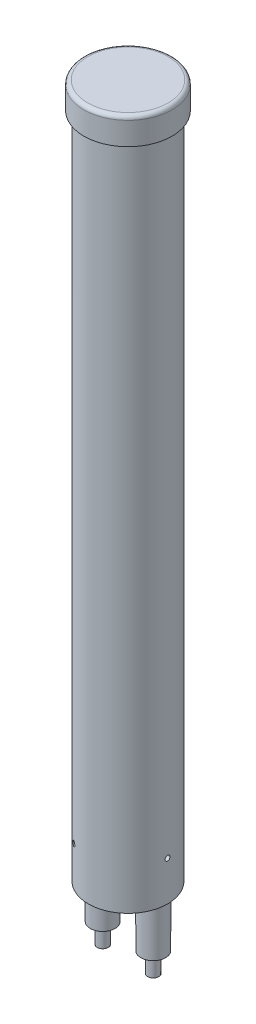
SolidWorks part; units mm, degrees
material "ABS"
ref_plane "Płaszczyzna przednia" through (0, 0, 0) normal (0, 0, 1) x (1, 0, 0)
ref_plane "Płaszczyzna górna" through (0, 0, 0) normal (0, 1, 0) x (1, 0, 0)
ref_plane "Płaszczyzna prawa" through (0, 0, 0) normal (1, 0, 0) x (0, 0, -1)
sketch "Sketch1" plane through (0, 0, 0) normal (0, 1, 0) x (1, 0, 0)
  circle A0 centre (0, 0) radius 20
  dimension "D1" = 40
extrude "Boss-Extrude1" add sketch "Sketch1" along normal blind 345
sketch "Sketch2" plane through (0, 345, 0) normal (0, 1, 0) x (1, 0, 0)
  circle A0 centre (0, 0) radius 22.25
  dimension "D1" = 44.5
extrude "Boss-Extrude2" add sketch "Sketch2" along normal blind 5 and the other way blind 8.5
fillet "Fillet1" radius 2 1 edges at (0, 350, 22.25)
ref_plane "Plane1" through (20, 0, 0) normal (1, 0, 0) x (0, 0, -1)
sketch "Sketch3" plane through (20, 0, 0) normal (1, 0, 0) x (0, 0, -1)
  line L0 (0, 0) -> (0, 20) construction
  circle A0 centre (0, 20) radius 1.25
  dimension "D2" = 2.5
  dimension "D1" = 20
extrude "Cut-Extrude1" cut sketch "Sketch3" against normal blind 5
pattern_circular "CirPattern1" count 3 every 120 about axis through (0, 345, 0) along (0, -1, 0) of "Cut-Extrude1"
sketch "Sketch4" plane through (0, 0, 0) normal (0, -1, 0) x (1, 0, 0)
  line L0 (12.75, 0) -> (0, 0) construction
  line L1 (0, 0) -> (-12.75, 0) construction
  circle A0 centre (-12.75, 0) radius 6.25
  circle A1 centre (12.75, 0) radius 6.25
  dimension "D1" = 25.5
  dimension "D2" = 12.5
extrude "Boss-Extrude3" add sketch "Sketch4" along normal blind 24
sketch "Sketch5" plane through (0, -24, 0) normal (0, -1, 0) x (1, 0, 0)
  circle A0 centre (-12.75, 0) radius 2.8
  circle A1 centre (12.75, 0) radius 2.8
  dimension "D1" = 5.6
extrude "Boss-Extrude4" add sketch "Sketch5" along normal blind 10
